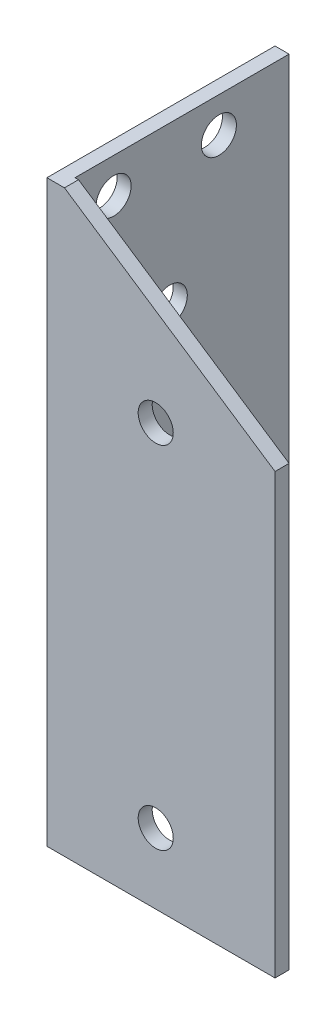
SolidWorks part; units mm, degrees
ref_plane "Спереди" through (0, 0, 0) normal (0, 0, 1) x (1, 0, 0)
ref_plane "Сверху" through (0, 0, 0) normal (0, 1, 0) x (1, 0, 0)
ref_plane "Справа" through (0, 0, 0) normal (1, 0, 0) x (0, 0, -1)
sketch "Эскиз1" plane through (0, 0, 0) normal (0, 1, 0) x (1, 0, 0)
  line L0 (0, 0) -> (65, 0)
  line L1 (0, 0) -> (0, 65)
extrude "Вытянуть-Тонкостенный1" add sketch "Эскиз1" along normal blind 165 thin thin type one direction wall 4
sketch "Эскиз2" plane through (0, 0, 0) normal (0, 0, 1) x (1, 0, 0)
  circle A0 centre (31, 120) radius 5
  circle A1 centre (31, 20) radius 5
  dimension "D1" = 2
extrude "Вырез-Вытянуть1" cut sketch "Эскиз2" against normal blind 10
sketch "Эскиз3" plane through (0, 0, 0) normal (-1, 0, 0) x (0, 0, 1)
  circle A0 centre (-31, 120) radius 5
  circle A1 centre (-31, 20) radius 5
  circle A2 centre (-15, 155) radius 5
  circle A3 centre (-45, 155) radius 5
  dimension "D1" = 2
  dimension "D2" = 2
extrude "Вырез-Вытянуть2" cut sketch "Эскиз3" against normal blind 10
sketch "Эскиз4" plane through (0, 0, 0) normal (0, 0, 1) x (1, 0, 0)
  line L0 (5, 165) -> (65, 125)
  line L1 (65, 165) -> (65, 0) construction
  line L2 (65, 165) -> (0, 165) construction
  line L3 (65, 125) -> (65, 165)
  line L4 (65, 165) -> (5, 165)
extrude "Вырез-Вытянуть3" cut sketch "Эскиз4" against normal through all
